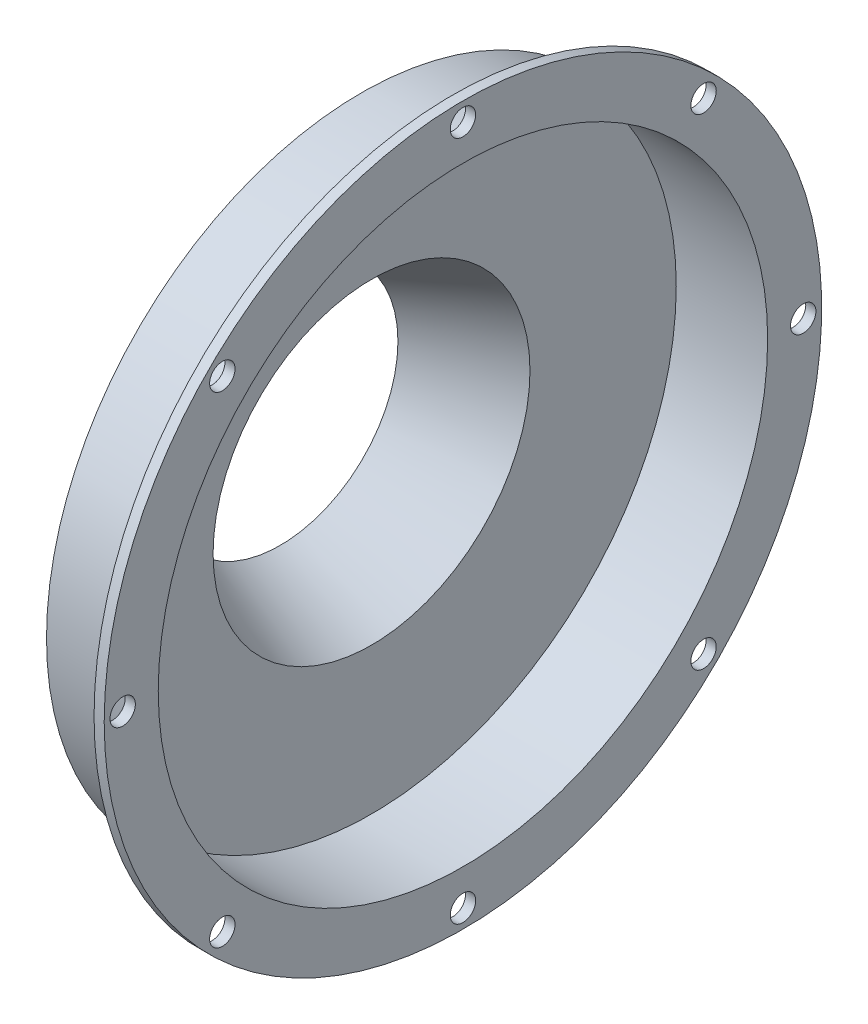
SolidWorks part; units mm, degrees
ref_plane "Front Plane" through (0, 0, 0) normal (0, 0, 1) x (1, 0, 0)
ref_plane "Top Plane" through (0, 0, 0) normal (0, 1, 0) x (1, 0, 0)
ref_plane "Right Plane" through (0, 0, 0) normal (1, 0, 0) x (0, 0, -1)
sketch "Sketch1" plane through (0, 0, 0) normal (0, 0, 1) x (1, 0, 0)
  line L0 (0, 0) -> (61.3012, 0) construction
  line L1 (0, 29.464) -> (22.86, 39.624)
  line L2 (22.86, 39.624) -> (22.86, 76.2)
  line L3 (22.86, 76.2) -> (45.72, 76.2)
  line L4 (45.72, 76.2) -> (45.72, 89.7128)
  line L5 (-1.0316, 31.7851) -> (20.32, 41.2747)
  line L6 (20.32, 41.2747) -> (20.32, 78.74)
  line L7 (20.32, 78.74) -> (43.18, 78.74)
  line L8 (43.18, 78.74) -> (43.18, 89.7128)
  line L9 (-1.0316, 31.7851) -> (0, 29.464)
  line L10 (43.18, 89.7128) -> (45.72, 89.7128)
  point P5 (30.6506, 0)
  dimension "D1" = 29.464
  dimension "D2" = 39.624
  dimension "D3" = 22.86
  dimension "D4" = 76.2
  dimension "D5" = 89.7128
  dimension "D7" = 22.86
  dimension "D6" = 2.54
revolve "Revolve1" add sketch "Sketch1" angle 360 about L0
sketch "Sketch2" plane through (43.18, 0, 0) normal (-1, 0, 0) x (0, 0, 1)
  circle A0 centre (0, 85.09) radius 3.175
  dimension "D1" = 6.35
  dimension "D2" = 85.09
extrude "Cut-Extrude1" cut sketch "Sketch2" against normal blind 2.54
pattern_circular "CirPattern1" count 8 over 360 about axis through (43.18, 0, 0) along (-1, 0, 0) of "Cut-Extrude1"
